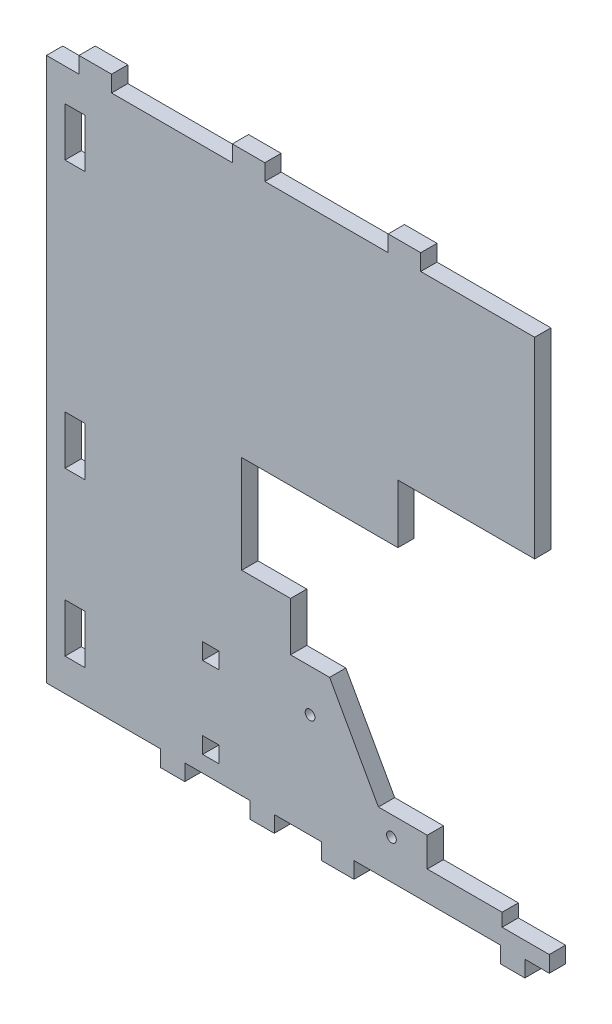
SolidWorks part; units mm, degrees
ref_plane "Plan de face" through (0, 0, 0) normal (0, 0, 1) x (1, 0, 0)
ref_plane "Plan de dessus" through (0, 0, 0) normal (0, 1, 0) x (1, 0, 0)
ref_plane "Plan de droite" through (0, 0, 0) normal (1, 0, 0) x (0, 0, -1)
sketch "Esquisse1" plane through (0, 0, 0) normal (0, 0, 1) x (1, 0, 0)
  line L1 (0, 0) -> (37, 0)
  line L2 (0, 0) -> (0, 45)
  line L3 (0, 45) -> (12, 45)
  line L4 (37, 0) -> (37, 18)
  line L6 (12, 45) -> (27, 18)
  line L7 (27, 18) -> (37, 18)
  circle A0 centre (6, 32) radius 1.5
  circle A1 centre (31, 12) radius 1.5
  dimension "D3" = 20
  dimension "D4" = 3
  dimension "D1" = 6
  dimension "D2" = 45
  dimension "D5" = 12
  dimension "D6" = 12
  dimension "D7" = 25
  dimension "D8" = 6
  dimension "D9" = 6
  dimension "D10" = 10
extrude "Boss.-Extru.1" add sketch "Esquisse1" along normal blind 5
sketch "Esquisse2" plane through (0, 0, 5) normal (0, 0, 1) x (1, 0, 0)
  line L0 (37, 18) -> (27, 18) construction
  line L2 (37, 0) -> (37, 18)
  line L3 (37, 0) -> (64.5, 0)
  line L4 (12, 45) -> (0, 45) construction
  line L5 (72, 0) -> (72, -5)
  line L6 (72, -5) -> (64.5, -5)
  line L7 (64.5, 0) -> (64.5, -5)
  line L8 (72, 0) -> (79.5, 0)
  line L12 (0, 0) -> (-5, 0)
  line L13 (0, 0) -> (0, 60)
  line L14 (0, 60) -> (-15, 60)
  line L15 (40, 167) -> (75, 167)
  line L16 (-12.5, 0) -> (-32.5, 0)
  line L17 (-40, 0) -> (-40, -5)
  line L18 (-15, 60) -> (-15, 90)
  line L19 (-40, -5) -> (-32.5, -5)
  line L20 (-75, 0) -> (-75, 167)
  line L21 (-75, 167) -> (-65, 167)
  line L22 (-32.5, 0) -> (-32.5, -5)
  line L23 (33, 90) -> (-15, 90)
  line L24 (75, 167) -> (75, 108)
  line L25 (-12.5, 0) -> (-12.5, -5)
  line L26 (-12.5, -5) -> (-5, -5)
  line L27 (-5, 0) -> (-5, -5)
  line L28 (-40, 0) -> (-75, 0)
  line L29 (-65, 167) -> (-65, 172)
  line L30 (-65, 172) -> (-55, 172)
  line L31 (-55, 167) -> (-55, 172)
  line L32 (-55, 167) -> (30, 167)
  line L33 (40, 167) -> (40, 172)
  line L34 (40, 172) -> (30, 172)
  line L35 (30, 167) -> (30, 172)
  line L36 (-69.2981, 10) -> (-63.1592, 10)
  line L37 (-69.2981, 10) -> (-69.2981, 25)
  line L38 (33, 90) -> (33, 108)
  line L39 (33, 108) -> (75, 108)
  line L40 (-63.1592, 10) -> (-63.1592, 25)
  line L41 (-69.2981, 25) -> (-63.1592, 25)
  line L42 (-69.2981, 10) -> (-69.2981, 0) construction
  line L43 (-63.1592, 25) -> (-63.1592, 10) construction
  line L45 (-69.2981, 75) -> (-63.1592, 75)
  line L46 (-69.2981, 75) -> (-69.2981, 60)
  line L47 (-69.2981, 60) -> (-63.1592, 60)
  line L48 (-63.1592, 75) -> (-63.1592, 60)
  line L49 (-69.2981, 142) -> (-63.1592, 142)
  line L50 (-69.2981, 142) -> (-69.2981, 157)
  line L51 (-69.2981, 157) -> (-63.1592, 157)
  line L52 (-63.1592, 142) -> (-63.1592, 157)
  line L53 (-22, 5) -> (-27, 5)
  line L54 (-22, 5) -> (-22, 10)
  line L55 (-22, 10) -> (-27, 10)
  line L56 (-27, 5) -> (-27, 10)
  line L57 (-27, 35) -> (-22, 35)
  line L58 (-27, 35) -> (-27, 30)
  line L59 (-27, 30) -> (-22, 30)
  line L60 (-22, 35) -> (-22, 30)
  line L62 (37, 18) -> (42, 18)
  line L63 (37, 18) -> (37, 8.9214)
  line L64 (65, 9) -> (65, 5)
  line L65 (42, 18) -> (42, 9)
  line L66 (65, 5) -> (79.5, 5)
  line L67 (79.5, 0) -> (79.5, 5)
  line L68 (65, 9) -> (42, 9)
  circle A0 centre (31, 12) radius 1.5 construction
  line M2 (0, 45) -> (0, 0)
  line M4 (37, 0) -> (37, 18)
  dimension "D24" = 11
  dimension "D25" = 3
  dimension "D1" = 42.5
  dimension "D3" = 27.5
  dimension "D4" = 4
  dimension "D5" = 5
  dimension "D6" = 15
  dimension "D7" = 15
  dimension "D8" = 167
  dimension "D9" = 18
  dimension "D10" = 5
  dimension "D11" = 20
  dimension "D12" = 75
  dimension "D13" = 75
  dimension "D14" = 5
  dimension "D15" = 10
  dimension "D16" = 85
  dimension "D17" = 10
  dimension "D18" = 48
  dimension "D19" = 10
  dimension "D20" = 15
  dimension "D21" = 35
  dimension "D22" = 10
  dimension "D23" = 30
  dimension "D26" = 5
  dimension "D27" = 23
  dimension "D28" = 7.5
extrude "Boss.-Extru.2" add sketch "Esquisse2" against normal blind 5 contours L64 L68 L65 L62 L2 L3 L7 L6 L5 L8 L67 L66 M4 | L38 L39 L24 L15 L33 L34 L35 L32 L31 L30 L29 L21 L20 L28 L17 L19 L22 L16 L25 L26 L27 L12 L13 L14 L18 L23 L53 L56 L55 L54 L52 L49 L50 L51 L37 L41 L40 L36 L45 L48 L47 L46 L57 L60 L59 M2 region at (55.1032, 4.4939, 5) region at (-16.1716, 98.7738, 5)
sketch "Esquisse3" plane through (0, 0, 0) normal (0, 0, -1) x (-1, 0, 0)
  line L0 (5, 0) -> (-64.5, 0) construction
  line L1 (-19.5, 0) -> (-9.5, 0)
  line L2 (-19.5, 0) -> (-19.5, -5)
  line L3 (-19.5, -5) -> (-9.5, -5)
  line L4 (-9.5, 0) -> (-9.5, -5)
  line L5 (-79.5, 0) -> (-79.5, 5) construction
  line L6 (55, 167) -> (-30, 167) construction
  line L7 (7.8934, 167) -> (17.8934, 167)
  line L8 (7.8934, 167) -> (7.8934, 172)
  line L9 (7.8934, 172) -> (17.8934, 172)
  line L10 (17.8934, 167) -> (17.8934, 172)
  dimension "D1" = 10
  dimension "D2" = 5
  dimension "D3" = 60
  dimension "D4" = 10
  dimension "D5" = 5
extrude "Boss.-Extru.3" add sketch "Esquisse3" against normal blind 5
